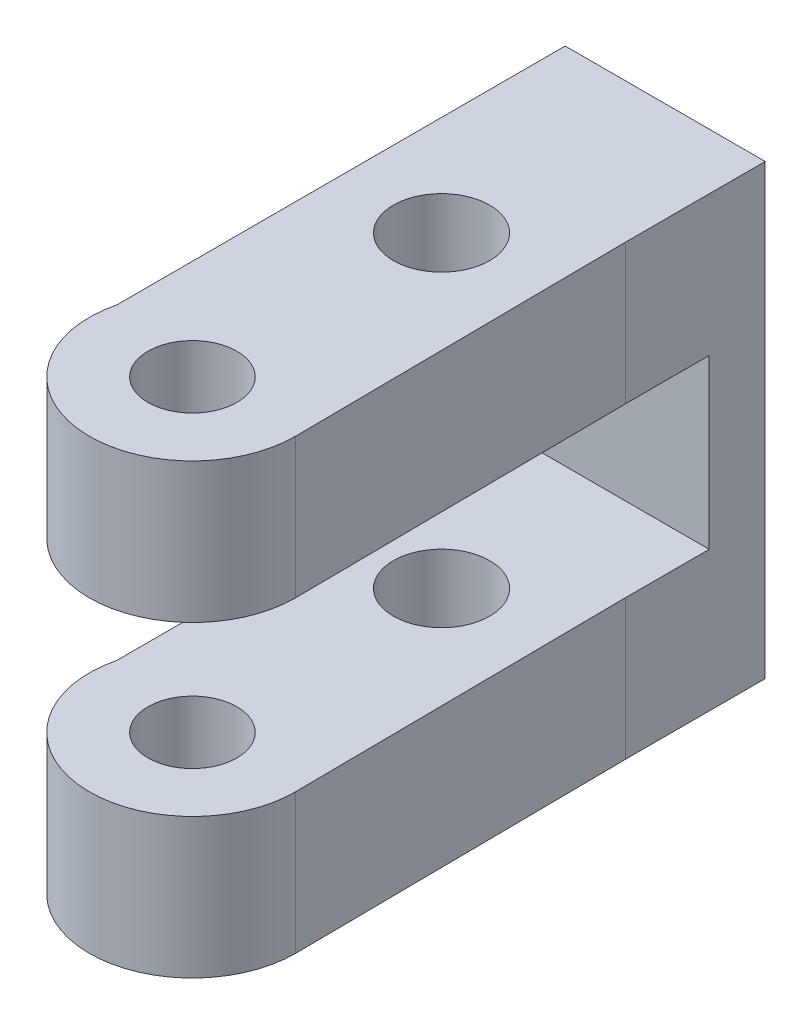
SolidWorks part; units mm, degrees
ref_plane "Front Plane" through (0, 0, 0) normal (0, 0, 1) x (1, 0, 0)
ref_plane "Top Plane" through (0, 0, 0) normal (0, 1, 0) x (1, 0, 0)
ref_plane "Right Plane" through (0, 0, 0) normal (1, 0, 0) x (0, 0, -1)
sketch "Croquis2" plane through (0, 0, 0) normal (0, 1, 0) x (1, 0, 0)
  line L0 (45, 0) -> (46.0553, 0) construction
  line L1 (-75, -40) -> (55, -40)
  line L2 (-75, -40) -> (-75, 40)
  line L3 (-75, 40) -> (55, 40)
  line L4 (75, -20) -> (75, 20)
  line L5 (45, 0) -> (46.0553, 0) construction
  line L6 (67, 26.7583) -> (67, -26.7583)
  line L7 (45, -30) -> (-50, -30)
  line L8 (45, -30) -> (45, 30)
  line L9 (45, 30) -> (-50, 30)
  line L10 (-50, -30) -> (-50, 30)
  line L11 (67, -26.7583) -> (67, 26.7583)
  line L13 (67, 26.7583) -> (61, 26.7583)
  line L15 (46.228, -1.6) -> (46.2586, -1.7343)
  line L16 (61.1553, 0) -> (61.0553, 0) construction
  line L17 (54.1602, 2.3742) -> (54.0439, 2.2986)
  line L18 (54.0439, 2.2986) -> (53.9684, 2.4149)
  line L19 (53.9087, 2.4244) -> (53.801, 2.3371)
  line L20 (53.801, 2.3371) -> (53.7137, 2.4449)
  line L21 (53.6534, 2.448) -> (53.5553, 2.35)
  line L22 (53.5553, 2.35) -> (53.4573, 2.448)
  line L23 (53.3969, 2.4449) -> (53.3097, 2.3371)
  line L24 (53.3097, 2.3371) -> (53.2019, 2.4244)
  line L25 (53.1422, 2.4149) -> (53.0667, 2.2986)
  line L26 (53.0667, 2.2986) -> (52.9505, 2.3742)
  line L27 (52.8921, 2.3585) -> (52.8291, 2.235)
  line L28 (52.8291, 2.235) -> (52.7056, 2.2979)
  line L29 (52.6492, 2.2763) -> (52.5995, 2.1468)
  line L30 (52.5995, 2.1468) -> (52.4701, 2.1965)
  line L31 (52.4162, 2.1691) -> (52.3803, 2.0352)
  line L32 (52.3803, 2.0352) -> (52.2464, 2.071)
  line L33 (52.1957, 2.0381) -> (52.174, 1.9012)
  line L34 (52.174, 1.9012) -> (52.0371, 1.9229)
  line L35 (51.9901, 1.8848) -> (51.9829, 1.7464)
  line L36 (51.9829, 1.7464) -> (51.8444, 1.7536)
  line L37 (51.8017, 1.7109) -> (51.8089, 1.5725)
  line L38 (51.8089, 1.5725) -> (51.6705, 1.5652)
  line L39 (51.6325, 1.5182) -> (51.6541, 1.3813)
  line L40 (51.6541, 1.3813) -> (51.5172, 1.3596)
  line L41 (51.4843, 1.3089) -> (51.5202, 1.175)
  line L42 (51.5202, 1.175) -> (51.3862, 1.1391)
  line L43 (51.3588, 1.0853) -> (51.4085, 0.9558)
  line L44 (51.4085, 0.9558) -> (51.2791, 0.9061)
  line L45 (51.2574, 0.8497) -> (51.3203, 0.7262)
  line L46 (51.3203, 0.7262) -> (51.1968, 0.6632)
  line L47 (51.1812, 0.6049) -> (51.2567, 0.4886)
  line L48 (51.2567, 0.4886) -> (51.1404, 0.4131)
  line L49 (51.1309, 0.3534) -> (51.2182, 0.2456)
  line L50 (51.2182, 0.2456) -> (51.1105, 0.1584)
  line L51 (51.1073, 0.098) -> (51.2053, 0)
  line L52 (51.2053, 0) -> (51.1073, -0.098)
  line L53 (51.1105, -0.1584) -> (51.2182, -0.2456)
  line L54 (51.2182, -0.2456) -> (51.1309, -0.3534)
  line L55 (51.1404, -0.4131) -> (51.2567, -0.4886)
  line L56 (51.2567, -0.4886) -> (51.1812, -0.6049)
  line L57 (51.1968, -0.6632) -> (51.3203, -0.7262)
  line L58 (51.3203, -0.7262) -> (51.2574, -0.8497)
  line L59 (51.2791, -0.9061) -> (51.4085, -0.9558)
  line L60 (51.4085, -0.9558) -> (51.3588, -1.0853)
  line L61 (51.3862, -1.1391) -> (51.5202, -1.175)
  line L62 (51.5202, -1.175) -> (51.4843, -1.3089)
  line L63 (51.5172, -1.3596) -> (51.6541, -1.3813)
  line L64 (51.6541, -1.3813) -> (51.6325, -1.5182)
  line L65 (51.6705, -1.5652) -> (51.8089, -1.5725)
  line L66 (51.8089, -1.5725) -> (51.8017, -1.7109)
  line L67 (51.8444, -1.7536) -> (51.9829, -1.7464)
  line L68 (51.9829, -1.7464) -> (51.9901, -1.8848)
  line L69 (52.0371, -1.9229) -> (52.174, -1.9012)
  line L70 (52.174, -1.9012) -> (52.1957, -2.0381)
  line L71 (52.2464, -2.071) -> (52.3803, -2.0352)
  line L72 (52.3803, -2.0352) -> (52.4162, -2.1691)
  line L73 (52.4701, -2.1965) -> (52.5995, -2.1468)
  line L74 (52.5995, -2.1468) -> (52.6492, -2.2763)
  line L75 (52.7056, -2.2979) -> (52.8291, -2.235)
  line L76 (52.8291, -2.235) -> (52.8921, -2.3585)
  line L77 (52.9505, -2.3742) -> (53.0667, -2.2986)
  line L78 (53.0667, -2.2986) -> (53.1422, -2.4149)
  line L79 (53.2019, -2.4244) -> (53.3097, -2.3371)
  line L80 (53.3097, -2.3371) -> (53.3969, -2.4449)
  line L81 (53.4573, -2.448) -> (53.5553, -2.35)
  line L82 (53.5553, -2.35) -> (53.6534, -2.448)
  line L83 (53.7137, -2.4449) -> (53.801, -2.3371)
  line L84 (53.801, -2.3371) -> (53.9087, -2.4244)
  line L85 (53.9684, -2.4149) -> (54.0439, -2.2986)
  line L86 (54.0439, -2.2986) -> (54.1602, -2.3742)
  line L87 (54.2186, -2.3585) -> (54.2815, -2.235)
  line L88 (54.2815, -2.235) -> (54.4051, -2.2979)
  line L89 (54.4615, -2.2763) -> (54.5112, -2.1468)
  line L90 (54.5112, -2.1468) -> (54.6406, -2.1965)
  line L91 (54.6944, -2.1691) -> (54.7303, -2.0352)
  line L92 (54.7303, -2.0352) -> (54.8643, -2.071)
  line L93 (54.9149, -2.0381) -> (54.9366, -1.9012)
  line L94 (54.9366, -1.9012) -> (55.0736, -1.9229)
  line L95 (55.1205, -1.8848) -> (55.1278, -1.7464)
  line L96 (55.1278, -1.7464) -> (55.2662, -1.7536)
  line L97 (55.309, -1.7109) -> (55.3017, -1.5725)
  line L98 (55.3017, -1.5725) -> (55.4402, -1.5652)
  line L99 (55.4782, -1.5182) -> (55.4565, -1.3813)
  line L100 (55.4565, -1.3813) -> (55.5935, -1.3596)
  line L101 (55.6264, -1.3089) -> (55.5905, -1.175)
  line L102 (55.5905, -1.175) -> (55.7244, -1.1391)
  line L103 (55.7518, -1.0853) -> (55.7022, -0.9558)
  line L104 (55.7022, -0.9558) -> (55.8316, -0.9061)
  line L105 (55.8533, -0.8497) -> (55.7903, -0.7262)
  line L106 (55.7903, -0.7262) -> (55.9138, -0.6632)
  line L107 (55.9295, -0.6049) -> (55.854, -0.4886)
  line L108 (55.854, -0.4886) -> (55.9703, -0.4131)
  line L109 (55.9797, -0.3534) -> (55.8925, -0.2456)
  line L110 (55.8925, -0.2456) -> (56.0002, -0.1584)
  line L111 (56.0034, -0.098) -> (55.9053, 0)
  line L112 (55.9053, 0) -> (56.0034, 0.098)
  line L113 (56.0002, 0.1584) -> (55.8925, 0.2456)
  line L114 (55.8925, 0.2456) -> (55.9797, 0.3534)
  line L115 (55.9703, 0.4131) -> (55.854, 0.4886)
  line L116 (55.854, 0.4886) -> (55.9295, 0.6049)
  line L117 (55.9138, 0.6632) -> (55.7903, 0.7262)
  line L118 (55.7903, 0.7262) -> (55.8533, 0.8497)
  line L119 (55.8316, 0.9061) -> (55.7022, 0.9558)
  line L120 (55.7022, 0.9558) -> (55.7518, 1.0853)
  line L121 (55.7244, 1.1391) -> (55.5905, 1.175)
  line L122 (55.5905, 1.175) -> (55.6264, 1.3089)
  line L123 (55.5935, 1.3596) -> (55.4565, 1.3813)
  line L124 (55.4565, 1.3813) -> (55.4782, 1.5182)
  line L125 (55.4402, 1.5652) -> (55.3017, 1.5725)
  line L126 (55.3017, 1.5725) -> (55.309, 1.7109)
  line L127 (55.2662, 1.7536) -> (55.1278, 1.7464)
  line L128 (55.1278, 1.7464) -> (55.1205, 1.8848)
  line L129 (55.0736, 1.9229) -> (54.9366, 1.9012)
  line L130 (54.9366, 1.9012) -> (54.9149, 2.0381)
  line L131 (54.8643, 2.071) -> (54.7303, 2.0352)
  line L132 (54.7303, 2.0352) -> (54.6944, 2.1691)
  line L133 (54.6406, 2.1965) -> (54.5112, 2.1468)
  line L134 (54.5112, 2.1468) -> (54.4615, 2.2763)
  line L135 (54.4051, 2.2979) -> (54.2815, 2.235)
  line L136 (54.2815, 2.235) -> (54.2186, 2.3585)
  line L137 (53.5553, 0) -> (53.5553, -7.5) construction
  line L139 (65.0006, 25.8237) -> (59.5501, 25.8237) construction
  line L141 (61.0553, 0) -> (67, 0) construction
  line L142 (59.0553, 0) -> (53.5553, 0) construction
  line L143 (48.0553, 0) -> (53.5553, 0) construction
  line L144 (48.0553, 0) -> (59.0553, 0) construction
  line L145 (60.701, 2.278) -> (60.8827, 1.6)
  line L146 (61, 24.889) -> (61, 23.889)
  line L149 (61, 22.0197) -> (61, 21.0197)
  line L152 (61, 19.1504) -> (61, 18.1504)
  line L154 (59.5501, 17.5667) -> (59.5501, 16.8648)
  line L155 (61, 16.2811) -> (61, 15.2811)
  line L157 (59.5501, 14.6974) -> (59.5501, 13.9955)
  line L158 (61, 13.4118) -> (61, 12.4118)
  line L160 (59.5501, 11.8282) -> (59.5501, 11.1262)
  line L161 (61, 10.5425) -> (61, 9.5425)
  line L163 (59.5501, 8.9589) -> (59.5501, 8.2569)
  line L164 (61, 7.6732) -> (61, 6.6732)
  line L166 (59.5501, 6.0896) -> (59.5501, 5.3876)
  line L167 (61, 4.8039) -> (61, 3.8039)
  line L169 (59.5501, 3.2203) -> (59.5501, 2.5183)
  line L170 (61, 1.9346) -> (61, 0.9346)
  line L172 (59.5501, 0.351) -> (59.5501, -0.351)
  line L173 (61, -0.9346) -> (61, -1.9346)
  line L175 (59.5501, -2.5183) -> (59.5501, -3.2203)
  line L176 (61, -3.8039) -> (61, -4.8039)
  line L178 (59.5501, -5.3876) -> (59.5501, -6.0896)
  line L179 (61, -6.6732) -> (61, -7.6732)
  line L181 (59.5501, -8.2569) -> (59.5501, -8.9589)
  line L182 (61, -9.5425) -> (61, -10.5425)
  line L184 (59.5501, -11.1262) -> (59.5501, -11.8282)
  line L185 (61, -12.4118) -> (61, -13.4118)
  line L187 (59.5501, -13.9955) -> (59.5501, -14.6974)
  line L188 (61, -15.2811) -> (61, -16.2811)
  line L190 (59.5501, -16.8648) -> (59.5501, -17.5667)
  line L191 (61, -18.1504) -> (61, -19.1504)
  line L194 (61, -21.0197) -> (61, -22.0197)
  line L197 (61, -23.889) -> (61, -24.889)
  line L200 (64, 26.7583) -> (64, 26.3977) construction
  line L203 (61, -26.7583) -> (67, -26.7583)
  line L204 (75, 20) -> (67, 20) construction
  line L205 (61, -26.7583) -> (61, -27.7583) [skipped]
  line L206 (-50, 0) -> (-75, 0) construction
  line L207 (75, -20) -> (67, -20) construction
  line L208 (50, -40) -> (50, 40) construction
  line L209 (50, -35) -> (50, -43.5216) construction
  line L210 (53.5731, -35) -> (53.5731, -46.0216)
  line L211 (46.4269, -35) -> (46.4269, -43.5216)
  line L212 (50.0036, 34.1275) -> (50.0036, 40.0656) construction
  line L213 (53.6852, 34.1275) -> (53.5731, 46.0216)
  line L214 (46.4269, 35) -> (46.4269, 43.5216)
  line L215 (-50, -30) -> (-47.1716, -27.1716) construction
  line L221 (-50, -30) -> (-47.1716, -30)
  line L222 (-50, -30) -> (-50, -27.1716)
  line L223 (46.4269, -43.5216) -> (46.4269, -51.0216)
  line L224 (53.5731, -46.0216) -> (53.5731, -51.0216)
  line L225 (46.4269, -51.0216) -> (53.5731, -51.0216)
  line L226 (53.5731, 46.0216) -> (53.5731, 51.0216)
  line L227 (46.4269, 43.5216) -> (46.4269, 51.0216)
  line L228 (46.4269, 51.0216) -> (53.5731, 51.0216)
  line L229 (50, 43.0304) -> (64, 23.3977) construction
  line L232 (46.4269, 51.0216) -> (53.5731, 51.0216)
  line L233 (46.4269, 51.0216) -> (46.4269, 49.0216)
  line L234 (53.5731, 51.0216) -> (53.5731, 49.0216)
  line L235 (46.4269, 49.0216) -> (53.5731, 49.0216)
  line L236 (46.4269, -49.0216) -> (53.5731, -49.0216)
  line L239 (61, 19.1504) -> (67, 19.1504)
  line L240 (61, 26.7583) -> (61, 19.1504)
  line L241 (50.0036, 40.0656) -> (61.1732, 24.4022)
  line L242 (52.8363, 42.0529) -> (64, 26.3977)
  line L243 (48.6009, 42.0327) -> (62.6009, 22.4) construction
  line L244 (51.4182, 44.0416) -> (65.4182, 24.409) construction
  line L245 (61, 24.889) -> (61, 26.7583)
  line L246 (64, 25.8237) -> (64, -26.7583) construction
  line L248 (-70.5, -35) -> (-54.5, -35)
  line L249 (61, -26.7583) -> (61, -19.1504)
  line L250 (61, -19.1504) -> (67, -19.1504)
  line L251 (-50, -27.1716) -> (-47.1716, -27.1716)
  line L252 (-47.1716, -30) -> (-47.1716, -27.1716)
  line L253 (-2.5, -30) -> (-2.5, 30) construction
  line L254 (-70.5, -35) -> (-70.5, -40)
  line L255 (-54.5, 35) -> (-70.5, 35)
  line L260 (-54.5, 35) -> (-54.5, -35)
  line L261 (-54.5, -35) -> (-70.5, -35)
  line L262 (-70.5, 35) -> (-70.5, -35)
  line L263 (-54.5, 35) -> (-70.5, -35) construction
  line L264 (-54.5, -35) -> (-70.5, 35) construction
  line L265 (-70.5, -40) -> (-54.5, -40)
  line L266 (-54.5, -35) -> (-54.5, -40)
  line L267 (-70.5, 35) -> (-54.5, 35)
  line L268 (-70.5, 35) -> (-70.5, 40)
  line L269 (-70.5, 40) -> (-54.5, 40)
  line L270 (-54.5, 35) -> (-54.5, 40)
  circle A0 centre (53.5553, 0) radius 7.5
  arc A1 (53.9684, 2.4149) -> (53.9087, 2.4244) centre (53.5553, 0) ccw
  arc A2 (53.7137, 2.4449) -> (53.6534, 2.448) centre (53.5553, 0) ccw
  arc A3 (53.4573, 2.448) -> (53.3969, 2.4449) centre (53.5553, 0) ccw
  arc A4 (53.2019, 2.4244) -> (53.1422, 2.4149) centre (53.5553, 0) ccw
  arc A5 (52.9505, 2.3742) -> (52.8921, 2.3585) centre (53.5553, 0) ccw
  arc A6 (52.7056, 2.2979) -> (52.6492, 2.2763) centre (53.5553, 0) ccw
  arc A7 (52.4701, 2.1965) -> (52.4162, 2.1691) centre (53.5553, 0) ccw
  arc A8 (52.2464, 2.071) -> (52.1957, 2.0381) centre (53.5553, 0) ccw
  arc A9 (52.0371, 1.9229) -> (51.9901, 1.8848) centre (53.5553, 0) ccw
  arc A10 (51.8444, 1.7536) -> (51.8017, 1.7109) centre (53.5553, 0) ccw
  arc A11 (51.6705, 1.5652) -> (51.6325, 1.5182) centre (53.5553, 0) ccw
  arc A12 (51.5172, 1.3596) -> (51.4843, 1.3089) centre (53.5553, 0) ccw
  arc A13 (51.3862, 1.1391) -> (51.3588, 1.0853) centre (53.5553, 0) ccw
  arc A14 (51.2791, 0.9061) -> (51.2574, 0.8497) centre (53.5553, 0) ccw
  arc A15 (51.1968, 0.6632) -> (51.1812, 0.6049) centre (53.5553, 0) ccw
  arc A16 (51.1404, 0.4131) -> (51.1309, 0.3534) centre (53.5553, 0) ccw
  arc A17 (51.1105, 0.1584) -> (51.1073, 0.098) centre (53.5553, 0) ccw
  arc A18 (51.1073, -0.098) -> (51.1105, -0.1584) centre (53.5553, 0) ccw
  arc A19 (51.1309, -0.3534) -> (51.1404, -0.4131) centre (53.5553, 0) ccw
  arc A20 (51.1812, -0.6049) -> (51.1968, -0.6632) centre (53.5553, 0) ccw
  arc A21 (51.2574, -0.8497) -> (51.2791, -0.9061) centre (53.5553, 0) ccw
  arc A22 (51.3588, -1.0853) -> (51.3862, -1.1391) centre (53.5553, 0) ccw
  arc A23 (51.4843, -1.3089) -> (51.5172, -1.3596) centre (53.5553, 0) ccw
  arc A24 (51.6325, -1.5182) -> (51.6705, -1.5652) centre (53.5553, 0) ccw
  arc A25 (51.8017, -1.7109) -> (51.8444, -1.7536) centre (53.5553, 0) ccw
  arc A26 (51.9901, -1.8848) -> (52.0371, -1.9229) centre (53.5553, 0) ccw
  arc A27 (52.1957, -2.0381) -> (52.2464, -2.071) centre (53.5553, 0) ccw
  arc A28 (52.4162, -2.1691) -> (52.4701, -2.1965) centre (53.5553, 0) ccw
  arc A29 (52.6492, -2.2763) -> (52.7056, -2.2979) centre (53.5553, 0) ccw
  arc A30 (52.8921, -2.3585) -> (52.9505, -2.3742) centre (53.5553, 0) ccw
  arc A31 (53.1422, -2.4149) -> (53.2019, -2.4244) centre (53.5553, 0) ccw
  arc A32 (53.3969, -2.4449) -> (53.4573, -2.448) centre (53.5553, 0) ccw
  arc A33 (53.6534, -2.448) -> (53.7137, -2.4449) centre (53.5553, 0) ccw
  arc A34 (53.9087, -2.4244) -> (53.9684, -2.4149) centre (53.5553, 0) ccw
  arc A35 (54.1602, -2.3742) -> (54.2186, -2.3585) centre (53.5553, 0) ccw
  arc A36 (54.4051, -2.2979) -> (54.4615, -2.2763) centre (53.5553, 0) ccw
  arc A37 (54.6406, -2.1965) -> (54.6944, -2.1691) centre (53.5553, 0) ccw
  arc A38 (54.8643, -2.071) -> (54.9149, -2.0381) centre (53.5553, 0) ccw
  arc A39 (55.0736, -1.9229) -> (55.1205, -1.8848) centre (53.5553, 0) ccw
  arc A40 (55.2662, -1.7536) -> (55.309, -1.7109) centre (53.5553, 0) ccw
  arc A41 (55.4402, -1.5652) -> (55.4782, -1.5182) centre (53.5553, 0) ccw
  arc A42 (55.5935, -1.3596) -> (55.6264, -1.3089) centre (53.5553, 0) ccw
  arc A43 (55.7244, -1.1391) -> (55.7518, -1.0853) centre (53.5553, 0) ccw
  arc A44 (55.8316, -0.9061) -> (55.8533, -0.8497) centre (53.5553, 0) ccw
  arc A45 (55.9138, -0.6632) -> (55.9295, -0.6049) centre (53.5553, 0) ccw
  arc A46 (55.9703, -0.4131) -> (55.9797, -0.3534) centre (53.5553, 0) ccw
  arc A47 (56.0002, -0.1584) -> (56.0034, -0.098) centre (53.5553, 0) ccw
  arc A48 (56.0034, 0.098) -> (56.0002, 0.1584) centre (53.5553, 0) ccw
  arc A49 (55.9797, 0.3534) -> (55.9703, 0.4131) centre (53.5553, 0) ccw
  arc A50 (55.9295, 0.6049) -> (55.9138, 0.6632) centre (53.5553, 0) ccw
  arc A51 (55.8533, 0.8497) -> (55.8316, 0.9061) centre (53.5553, 0) ccw
  arc A52 (55.7518, 1.0853) -> (55.7244, 1.1391) centre (53.5553, 0) ccw
  arc A53 (55.6264, 1.3089) -> (55.5935, 1.3596) centre (53.5553, 0) ccw
  arc A54 (55.4782, 1.5182) -> (55.4402, 1.5652) centre (53.5553, 0) ccw
  arc A55 (55.309, 1.7109) -> (55.2662, 1.7536) centre (53.5553, 0) ccw
  arc A56 (55.1205, 1.8848) -> (55.0736, 1.9229) centre (53.5553, 0) ccw
  arc A57 (54.9149, 2.0381) -> (54.8643, 2.071) centre (53.5553, 0) ccw
  arc A58 (54.6944, 2.1691) -> (54.6406, 2.1965) centre (53.5553, 0) ccw
  arc A59 (54.4615, 2.2763) -> (54.4051, 2.2979) centre (53.5553, 0) ccw
  arc A60 (54.2186, 2.3585) -> (54.1602, 2.3742) centre (53.5553, 0) ccw
  circle A61 centre (53.5553, 0) radius 2.25
  arc A62 (55, 40) -> (75, 20) centre (55, 20) cw
  arc A63 (55, -40) -> (75, -20) centre (55, -20) ccw
  circle A64 centre (53.5553, 0) radius 5.5
  arc A65 (54.0553, -5.4772) -> (55.1553, -7.3273) centre (59.6317, -3.4139) ccw
  arc A66 (53.0553, -5.4772) -> (51.9553, -7.3273) centre (47.479, -3.4139) cw
  arc A67 (50.3837, -4.4934) -> (48.506, -5.5457) centre (46.5861, 0.0817) cw
  arc A68 (51.2497, -4.9934) -> (51.2773, -7.1457) centre (57.1107, -5.9946) ccw
  arc A69 (48.5619, -2.3056) -> (46.4097, -2.278) centre (47.5607, 3.5553) cw
  arc A70 (49.0619, -3.1716) -> (48.0097, -5.0493) centre (53.637, -6.9692) ccw
  arc A71 (48.0781, 0.5) -> (46.228, 1.6) centre (50.1415, 6.0763) cw
  arc A72 (48.0781, -0.5) -> (46.228, -1.6) centre (50.1415, -6.0763) ccw
  arc A73 (49.0619, 3.1716) -> (48.0097, 5.0493) centre (53.637, 6.9692) cw
  arc A74 (48.5619, 2.3056) -> (46.4097, 2.278) centre (47.5607, -3.5553) ccw
  arc A75 (51.2497, 4.9934) -> (51.2773, 7.1457) centre (57.1107, 5.9946) cw
  arc A76 (50.3837, 4.4934) -> (48.506, 5.5457) centre (46.5861, -0.0817) ccw
  arc A77 (54.0553, 5.4772) -> (55.1553, 7.3273) centre (59.6317, 3.4139) cw
  arc A78 (53.0553, 5.4772) -> (51.9553, 7.3273) centre (47.479, 3.4139) ccw
  arc A79 (56.727, 4.4934) -> (58.6046, 5.5457) centre (60.5245, -0.0817) cw
  arc A80 (55.8609, 4.9934) -> (55.8334, 7.1457) centre (50, 5.9946) ccw
  arc A81 (58.5487, 2.3056) -> (60.701, 2.278) centre (59.55, -3.5553) cw
  arc A82 (58.0487, 3.1716) -> (59.101, 5.0493) centre (53.4736, 6.9692) ccw
  arc A83 (59.0326, -0.5) -> (60.8827, -1.6) centre (56.9692, -6.0763) cw
  arc A84 (59.0326, 0.5) -> (60.8827, 1.6) centre (56.9692, 6.0763) ccw
  arc A85 (58.0487, -3.1716) -> (59.101, -5.0493) centre (53.4736, -6.9692) cw
  arc A86 (58.5487, -2.3056) -> (60.701, -2.278) centre (59.55, 3.5553) ccw
  arc A89 (55.8609, -4.9934) -> (55.8334, -7.1457) centre (50, -5.9946) cw
  arc A90 (56.727, -4.4934) -> (58.6046, -5.5457) centre (60.5245, 0.0817) ccw
  arc A95 (61, 16.2811) -> (59.5501, 16.8648) centre (62.2327, 21.4358) cw
  arc A96 (61, 18.1504) -> (59.5501, 17.5667) centre (62.2327, 12.9958) ccw
  arc A97 (61, 13.4118) -> (59.5501, 13.9955) centre (62.2327, 18.5665) cw
  arc A98 (61, 15.2811) -> (59.5501, 14.6974) centre (62.2327, 10.1265) ccw
  arc A99 (61, 10.5425) -> (59.5501, 11.1262) centre (62.2327, 15.6972) cw
  arc A100 (61, 12.4118) -> (59.5501, 11.8282) centre (62.2327, 7.2572) ccw
  arc A101 (61, 7.6732) -> (59.5501, 8.2569) centre (62.2327, 12.8279) cw
  arc A102 (61, 9.5425) -> (59.5501, 8.9589) centre (62.2327, 4.3879) ccw
  arc A103 (61, 4.8039) -> (59.5501, 5.3876) centre (62.2327, 9.9586) cw
  arc A104 (61, 6.6732) -> (59.5501, 6.0896) centre (62.2327, 1.5186) ccw
  arc A105 (61, 1.9346) -> (59.5501, 2.5183) centre (62.2327, 7.0893) cw
  arc A106 (61, 3.8039) -> (59.5501, 3.2203) centre (62.2327, -1.3507) ccw
  arc A107 (61, -0.9346) -> (59.5501, -0.351) centre (62.2327, 4.22) cw
  arc A108 (61, 0.9346) -> (59.5501, 0.351) centre (62.2327, -4.22) ccw
  arc A109 (61, -3.8039) -> (59.5501, -3.2203) centre (62.2327, 1.3507) cw
  arc A110 (61, -1.9346) -> (59.5501, -2.5183) centre (62.2327, -7.0893) ccw
  arc A111 (61, -6.6732) -> (59.5501, -6.0896) centre (62.2327, -1.5186) cw
  arc A112 (61, -4.8039) -> (59.5501, -5.3876) centre (62.2327, -9.9586) ccw
  arc A113 (61, -9.5425) -> (59.5501, -8.9589) centre (62.2327, -4.3879) cw
  arc A114 (61, -7.6732) -> (59.5501, -8.2569) centre (62.2327, -12.8279) ccw
  arc A115 (61, -12.4118) -> (59.5501, -11.8282) centre (62.2327, -7.2572) cw
  arc A116 (61, -10.5425) -> (59.5501, -11.1262) centre (62.2327, -15.6972) ccw
  arc A117 (61, -15.2811) -> (59.5501, -14.6974) centre (62.2327, -10.1265) cw
  arc A118 (61, -13.4118) -> (59.5501, -13.9955) centre (62.2327, -18.5665) ccw
  arc A119 (61, -18.1504) -> (59.5501, -17.5667) centre (62.2327, -12.9958) cw
  arc A120 (61, -16.2811) -> (59.5501, -16.8648) centre (62.2327, -21.4358) ccw
  circle A128 centre (64, -23.889) radius 1.5875
  circle A129 centre (64, 23.3977) radius 1.5875
  circle A130 centre (69.4482, 20) radius 2.175
  circle A131 centre (69.4482, -20) radius 2.175
  circle A132 centre (50, -35) radius 1.5875
  circle A133 centre (50.0036, 34.1275) radius 1.5875
  arc A134 (53.5731, -35) -> (46.4269, -35) centre (50, -35) ccw
  arc A136 (53.6852, 34.1275) -> (46.4269, 35) centre (50.0036, 34.1275) cw
  circle A138 centre (50, 43.0304) radius 1.7203
  circle A139 centre (50, -43.5216) radius 1.7203
  arc A142 (52.4426, 44.7721) -> (47.5574, 41.2886) centre (50, 43.0304) ccw
  arc A143 (61.5574, 21.6559) -> (66.4426, 25.1395) centre (64, 23.3977) ccw
  arc A144 (52.8363, 42.0529) -> (50.0286, 40.0305) centre (50, 43.0304) ccw
  arc A145 (61.1732, 24.4022) -> (64, 26.3977) centre (64, 23.3977) ccw
  arc A146 (62.2582, 25.8403) -> (62.2351, 25.8237) centre (64, 23.3977) ccw
  circle A151 centre (-47.1716, -27.1716) radius 2
  circle A152 centre (42.1716, -27.1716) radius 2
  circle A153 centre (42.1716, 27.1716) radius 2
  circle A154 centre (-47.1716, 27.1716) radius 2
  point P5 (65.0006, 25.8237)
  point P6 (0, 0)
  point P13 (67, 0)
  point P20 (59.8563, -29.3308)
  point P216 (53.5553, -7.5)
  point P221 (53.5553, -5.5)
  point P283 (53.5553, 0)
  point P290 (59.5501, 25.8237)
  point P292 (61, 24.889)
  point P297 (53.5553, 0)
  point P409 (-62.5, 0)
  point P411 (-62.5, 0)
  point P415 (-62.5, 0)
  point P424 (50, -39.2608)
  point P434 (50, 39.2608)
  point P453 (57, 33.214)
  dimension "D6" = 15
  dimension "D9" = 6
  dimension "D10" = 11
  dimension "D13" = 30
  dimension "D20" = 1
  dimension "D22" = 3.175
  dimension "D23" = 3.175
  dimension "D8" = 4.35
  dimension "D25" = 3.175
  dimension "D30" = 5
  dimension "D32" = 3
  dimension "D18" = 4
  dimension "D2" = 80
  dimension "D3" = 30
  dimension "D4" = 60
  dimension "D5" = 12
  dimension "D7" = 8.5553
  dimension "D11" = 0.5
  dimension "D12" = 1.6
  dimension "D14" = 4
  dimension "D15" = 95
  dimension "2.25" = 22
  dimension "D16" = 1.8693
  dimension "D17" = 1.8693
  dimension "D19" = 0.702
  dimension "D24" = 16
  dimension "D26" = 5
  dimension "D27" = 5
  dimension "D28" = 130
  dimension "D29" = 7.5
  dimension "D31" = 2
  dimension "D21" = 19
extrude "Saliente-Extruir1" add sketch "Croquis2" against normal blind 5 contours A144 L242 L213 L226 L235 L227 L214 L3 L241 A142 | L242 A144 A142 L241 L3 L213 A138 | A136 L213 L241 L3 L214 A133 | L3 L241 L213 region at (49.8017, 0, -46.0702) region at (48.2387, 0, -39.8794) region at (50.1125, 0, -40.0673) region at (52.4527, 0, -38.3044)
extrude "Saliente-Extruir2" add sketch "Croquis2<4>" against normal blind 11 contours L227 L235 L226 L228 region at (50, 0, -50.0216)
sketch "Croquis2<4>" plane through (0, 0, 0) normal (0, 1, 0) x (1, 0, 0) same geometry as "Croquis2"
extrude "Saliente-Extruir3" add sketch "Croquis2<5>" against normal blind 5 from offset 11 contours A144 L242 L213 L226 L235 L227 L214 L3 L241 A142 | L227 L235 L226 L228 | L242 A144 A142 L241 L3 L213 A138 | A136 L213 L241 L3 L214 A133 | L3 L241 L213 region at (49.8017, 0, -46.0702) region at (48.2387, 0, -39.8794) region at (50.1125, 0, -40.0673) region at (52.4527, 0, -38.3044) region at (50, 0, -50.0216) offset against normal yes
sketch "Croquis2<5>" plane through (0, 0, 0) normal (0, 1, 0) x (1, 0, 0) same geometry as "Croquis2"
